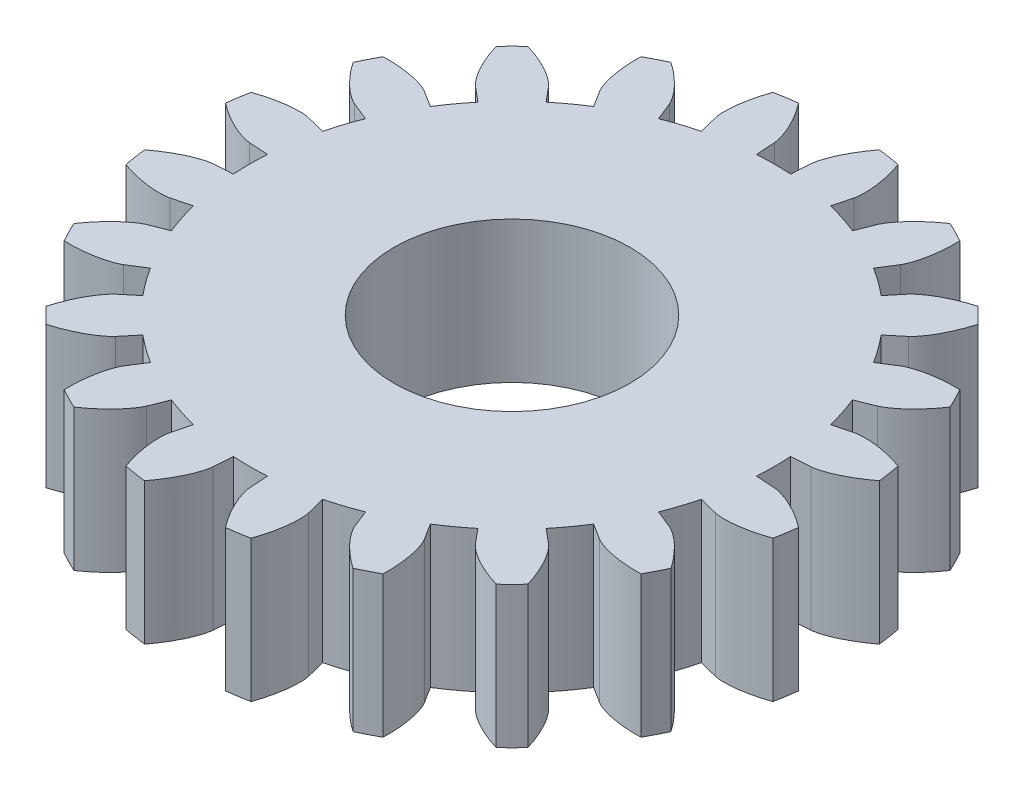
SolidWorks part; units mm, degrees
ref_plane "Front Plane" through (0, 0, 0) normal (0, 0, 1) x (1, 0, 0)
ref_plane "Top Plane" through (0, 0, 0) normal (0, 1, 0) x (1, 0, 0)
ref_plane "Right Plane" through (0, 0, 0) normal (1, 0, 0) x (0, 0, -1)
ref_plane "Bottom Plane" through (0, 0, 0) normal (0, 1, 0) x (1, 0, 0)
sketch "Sketch1" plane through (0, 0, 0) normal (0, 1, 0) x (1, 0, 0)
  line L0 (0, 0) -> (-0.7753, 11.9089)
  line L1 (0, 0) -> (0.7753, 11.9089)
  line L2 (0, 0) -> (0, 13.97) construction
  line L3 (0, 0) -> (0.9964, 12.6609) construction
  line L4 (0, 0) -> (-0.9964, 12.6609) construction
  circle A0 centre (0, 0) radius 12.7 construction
  circle A1 centre (0, 0) radius 11.9341 construction
  circle A2 centre (0, 0) radius 13.97
  circle A3 centre (0, 0) radius 11.1125
  circle A4 centre (0, 0) radius 5
  spline S0 degree 4 poles (0.7753, 11.9089) (0.7759, 11.9177) (0.7781, 11.9423) (0.7845, 11.9888) (0.7981, 12.064) (0.8202, 12.1591) (0.8542, 12.2809) (0.9009, 12.4227) (0.9594, 12.5765) (1.0305, 12.7413) (1.108, 12.9034) (1.1913, 13.0626) (1.2798, 13.2189) (1.3931, 13.4053) (1.5376, 13.6246) (1.7188, 13.8742) (1.9385, 14.1491) (2.1771, 14.4197) (2.4237, 14.678) (2.686, 14.929) (2.949, 15.1648) (3.2348, 15.3989) (3.5052, 15.6094) (3.8213, 15.8326) (4.0803, 16.009) (4.4353, 16.2277) (4.649, 16.3526) (4.9034, 16.4937) (5.0186, 16.5538) (5.0895, 16.5908) knots 0 0 0 0 0 0.005377 0.015084 0.028532 0.04661 0.064855 0.092111 0.119476 0.146842 0.174209 0.201575 0.228941 0.256307 0.307035 0.361767 0.4165 0.471232 0.525964 0.580697 0.635429 0.690161 0.744894 0.799626 0.854358 0.909091 0.954545 1 1 1 1 1 construction
  spline S1 degree 4 poles (0.7753, 11.9089) (0.7759, 11.9177) (0.7781, 11.9423) (0.7845, 11.9888) (0.7981, 12.064) (0.8202, 12.1591) (0.8542, 12.2809) (0.9009, 12.4227) (0.9594, 12.5765) (1.0305, 12.7413) (1.108, 12.9034) (1.1913, 13.0626) (1.2798, 13.2189) (1.3931, 13.4053) (1.5376, 13.6246) (1.7188, 13.8742) (1.9385, 14.1491) (2.1771, 14.4197) (2.4237, 14.678) (2.686, 14.929) (2.949, 15.1648) (3.2348, 15.3989) (3.5052, 15.6094) (3.8213, 15.8326) (4.0803, 16.009) (4.3584, 16.1803) (4.4952, 16.262) (4.5658, 16.3031) knots 0 0 0 0 0 0.005377 0.015084 0.028532 0.04661 0.064855 0.092111 0.119476 0.146842 0.174209 0.201575 0.228941 0.256307 0.307035 0.361767 0.4165 0.471232 0.525964 0.580697 0.635429 0.690161 0.744894 0.799626 0.854358 0.909091 0.909091 0.909091 0.909091 0.909091
  spline S2 degree 4 poles (-0.7753, 11.9089) (-0.7759, 11.9177) (-0.7781, 11.9423) (-0.7845, 11.9888) (-0.7981, 12.064) (-0.8202, 12.1591) (-0.8542, 12.2809) (-0.9009, 12.4227) (-0.9594, 12.5765) (-1.0305, 12.7413) (-1.108, 12.9034) (-1.1913, 13.0626) (-1.2798, 13.2189) (-1.3931, 13.4053) (-1.5376, 13.6246) (-1.7188, 13.8742) (-1.9385, 14.1491) (-2.1771, 14.4197) (-2.4237, 14.678) (-2.686, 14.929) (-2.949, 15.1648) (-3.2348, 15.3989) (-3.5052, 15.6094) (-3.8213, 15.8326) (-4.0803, 16.009) (-4.4353, 16.2277) (-4.649, 16.3526) (-4.9034, 16.4937) (-5.0186, 16.5538) (-5.0895, 16.5908) knots 0 0 0 0 0 0.005377 0.015084 0.028532 0.04661 0.064855 0.092111 0.119476 0.146842 0.174209 0.201575 0.228941 0.256307 0.307035 0.361767 0.4165 0.471232 0.525964 0.580697 0.635429 0.690161 0.744894 0.799626 0.854358 0.909091 0.954545 1 1 1 1 1 construction
  spline S3 degree 4 poles (-0.7753, 11.9089) (-0.7759, 11.9177) (-0.7781, 11.9423) (-0.7845, 11.9888) (-0.7981, 12.064) (-0.8202, 12.1591) (-0.8542, 12.2809) (-0.9009, 12.4227) (-0.9594, 12.5765) (-1.0305, 12.7413) (-1.108, 12.9034) (-1.1913, 13.0626) (-1.2798, 13.2189) (-1.3931, 13.4053) (-1.5376, 13.6246) (-1.7188, 13.8742) (-1.9385, 14.1491) (-2.1771, 14.4197) (-2.4237, 14.678) (-2.686, 14.929) (-2.949, 15.1648) (-3.2348, 15.3989) (-3.5052, 15.6094) (-3.8213, 15.8326) (-4.0803, 16.009) (-4.3584, 16.1803) (-4.4952, 16.262) (-4.5658, 16.3031) knots 0 0 0 0 0 0.005377 0.015084 0.028532 0.04661 0.064855 0.092111 0.119476 0.146842 0.174209 0.201575 0.228941 0.256307 0.307035 0.361767 0.4165 0.471232 0.525964 0.580697 0.635429 0.690161 0.744894 0.799626 0.854358 0.909091 0.909091 0.909091 0.909091 0.909091
  dimension "D1" = 25.4
  dimension "D2" = 23.8682
  dimension "D7" = 10
  dimension "D3" = 1.27
  dimension "D4" = 1.5875
  dimension "D5" = 4.5
  dimension "D6" = 4.5
extrude "Boss-Extrude1" add sketch "Sketch1" along normal blind 6 contours A2 | A4
extrude "Cut-Extrude1" cut sketch "Sketch1<3>" against normal up to surface from surface contours S3 L0 A3 L1 S1 A2 region at (0, 0, -12.7515) up to face at (0, 0, 13.97) starting at face at (0, 6, 13.97)
sketch "Sketch1<3>" plane through (0, 0, 0) normal (0, 1, 0) x (1, 0, 0) same geometry as "Sketch1"
pattern_circular "CirPattern1" count 20 over 360 about axis through (0, 6, 0) along (0, -1, 0) of "Cut-Extrude1"
equation "\"Module\"= 1.270mm'20dp = 1.270mod | 32dp = 0.7938mod"
equation "\"Teeth\"= 20"
equation "\"Tooth Width\"= 6mm"
equation "\"Pressure Angle\"= 20deg"
equation "\"D1@Sketch1\"=\"Module\"*\"Teeth\""
equation "\"D2@Sketch1\"=\"D1@Sketch1\"*cos(\"Pressure Angle\")"
equation "\"D3@Sketch1\"=\"Module\""
equation "\"D4@Sketch1\"=1.25*\"Module\""
equation "\"D5@Sketch1\"=360/(\"Teeth\"*4)"
equation "\"D6@Sketch1\"=\"D5@Sketch1\""
equation "\"D1@Boss-Extrude1\"=\"Tooth Width\""
equation "\"D1@CirPattern1\"=\"Teeth\""
